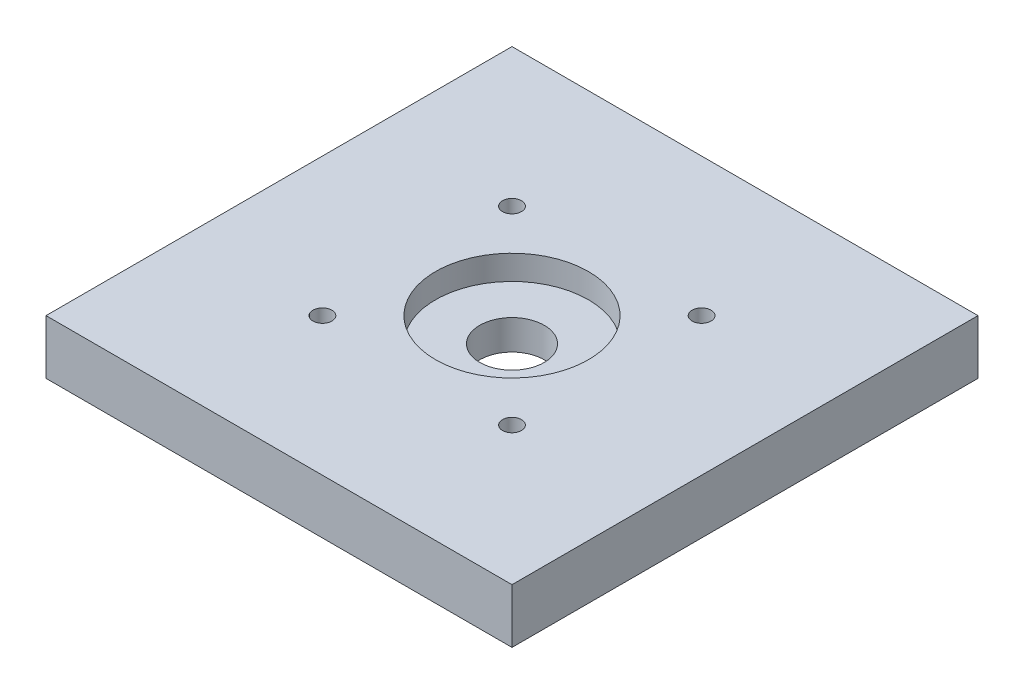
SolidWorks part; units mm, degrees
ref_plane "Front Plane" through (0, 0, 0) normal (0, 0, 1) x (1, 0, 0)
ref_plane "Top Plane" through (0, 0, 0) normal (0, 1, 0) x (1, 0, 0)
ref_plane "Right Plane" through (0, 0, 0) normal (1, 0, 0) x (0, 0, -1)
sketch "Sketch1" plane through (0, 0, 0) normal (0, 1, 0) x (1, 0, 0)
  line L5 (-38.1, 38.1) -> (38.1, 38.1)
  line L6 (-38.1, 38.1) -> (-38.1, -38.1)
  line L7 (-38.1, -38.1) -> (38.1, -38.1)
  line L8 (38.1, 38.1) -> (38.1, -38.1)
  line L9 (-38.1, 38.1) -> (38.1, -38.1) construction
  line L10 (-38.1, -38.1) -> (38.1, 38.1) construction
  circle A0 centre (-15.5, -15.5) radius 1.55
  circle A1 centre (15.5, -15.5) radius 1.55
  circle A2 centre (15.5, 15.5) radius 1.55
  circle A3 centre (-15.5, 15.5) radius 1.55
  circle A4 centre (-1.3312, 1.3512) radius 0.0101
  circle A7 centre (0, 0) radius 5.2705
  point P0 (0, 0)
  point P14 (0, 0)
  dimension "D4" = 3.1
  dimension "D5" = 10.541
  dimension "D1" = 76.2
  dimension "D2" = 76.2
  dimension "D3" = 31
extrude "Boss-Extrude1" add sketch "Sketch1" along normal blind 8.89 contours L8 L5 L6 L7 A7 A3 A2 A1 A0 region at (0, 0, -37.0224)
sketch "Sketch2" plane through (0, 8.89, 0) normal (0, 1, 0) x (1, 0, 0)
  circle A0 centre (0, 0) radius 12.5
  dimension "D1" = 25
extrude "Cut-Extrude1" cut sketch "Sketch2" against normal blind 4
